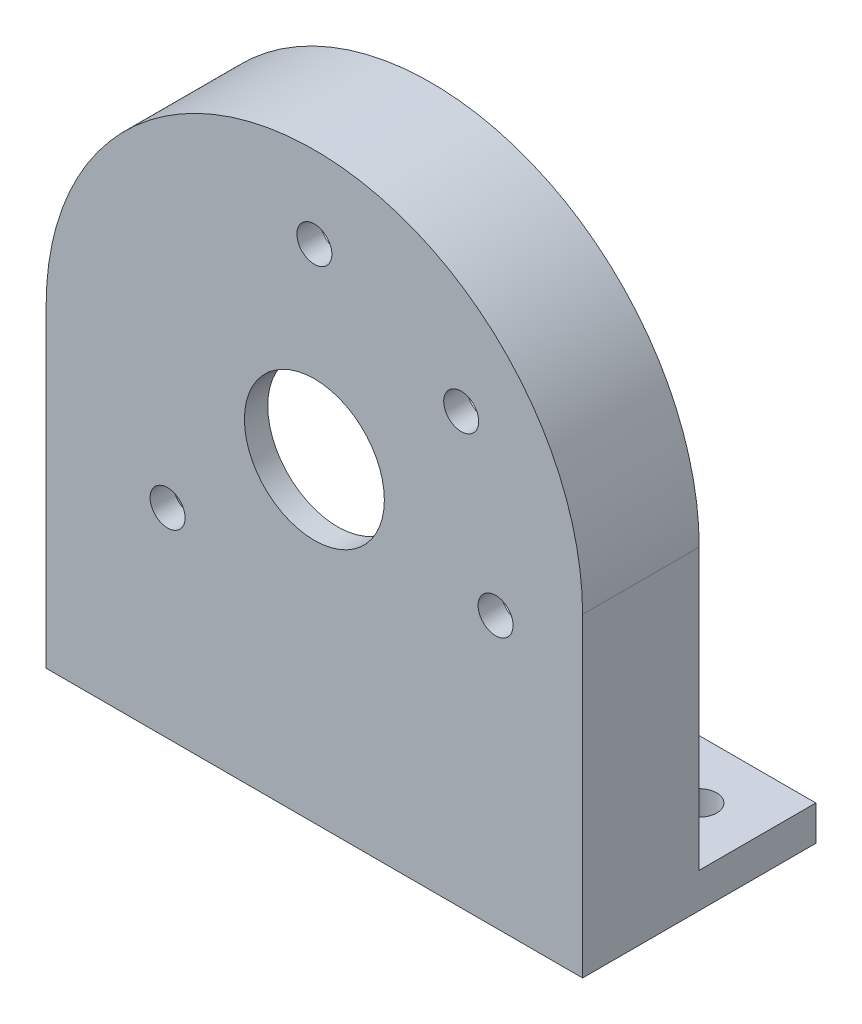
SolidWorks part; units mm, degrees
ref_plane "前视基准面" through (0, 0, 0) normal (0, 0, 1) x (1, 0, 0)
ref_plane "上视基准面" through (0, 0, 0) normal (0, 1, 0) x (1, 0, 0)
ref_plane "右视基准面" through (0, 0, 0) normal (1, 0, 0) x (0, 0, -1)
other "Configuration Table"
sketch "草图1" plane through (0, 0, 0) normal (0, 0, 1) x (1, 0, 0)
  line L0 (-23, 0) -> (-23, -27)
  line L1 (-23, -27) -> (23, -27)
  line L2 (23, -27) -> (23, 0)
  arc A1 (23, 0) -> (-23, 0) centre (0, 0) ccw
  dimension "D1" = 27
  dimension "D2" = 23
extrude "凸台-拉伸1" add sketch "草图1" along normal blind 20
sketch "草图2" plane through (0, 0, 0) normal (0, 0, -1) x (-1, 0, 0)
  line L0 (-23, -24) -> (23, -24)
  line L1 (23, 0) -> (23, -27) construction
  line L2 (-23, -27) -> (-23, 0) construction
  line L3 (-23, 0) -> (-23, -27)
  line L4 (-23, -27) -> (23, -27)
  line L5 (23, -27) -> (23, 0)
  line L6 (-23, 0) -> (-23, -24)
  line L8 (23, -24) -> (23, 0)
  arc A1 (23, 0) -> (-23, 0) centre (0, 0) ccw
  arc A2 (23, 0) -> (-23, 0) centre (0, 0) ccw
  dimension "D2" = 24
  dimension "D1" = 0
extrude "切除-拉伸1" cut sketch "草图2" against normal blind 10
sketch "草图3" plane through (0, 0, 10) normal (0, 0, -1) x (-1, 0, 0)
  circle A0 centre (0, 0) radius 21
extrude "切除-拉伸2" cut sketch "草图3" against normal blind 8
sketch "草图6" plane through (0, -27, 0) normal (0, -1, 0) x (1, 0, 0)
  line L0 (-23, 20) -> (-23, 0) construction
  line L1 (-23, 20) -> (23, 20) construction
  line L2 (0, -55) -> (0, 55) construction
  line L3 (-27.5378, 10) -> (27.2593, 10) construction
  circle A0 centre (-18, 15) radius 1.5
  circle A1 centre (18, 15) radius 1.5
  circle A2 centre (18, 5) radius 1.5
  circle A3 centre (-18, 5) radius 1.5
  dimension "D1" = 5
  dimension "D2" = 5
  dimension "D3" = 10
extrude "切除-拉伸3" cut sketch "草图6" against normal blind 5
sketch "草图7" plane through (0, 0, 20) normal (0, 0, 1) x (1, 0, 0)
  circle A0 centre (0, 16) radius 1.5 construction
  circle A1 centre (0, 16) radius 1.5
  circle A2 centre (12.5891, 9.875) radius 1.5 construction
  circle A3 centre (12.5891, 9.875) radius 1.5
  circle A4 centre (-12.5891, -9.875) radius 1.5 construction
  circle A5 centre (15.5396, -3.8105) radius 1.5 construction
  circle A6 centre (-12.5891, -9.875) radius 1.5
  circle A7 centre (15.5396, -3.8105) radius 1.5
extrude "切除-拉伸6" cut sketch "草图7" against normal blind 3
sketch "草图8" plane through (0, 0, 18) normal (0, 0, -1) x (-1, 0, 0)
  circle A1 centre (0, 0) radius 6
  circle A2 centre (0, 0) radius 6
  dimension "D1" = 0
extrude "切除-拉伸7" cut sketch "草图8" against normal blind 3
